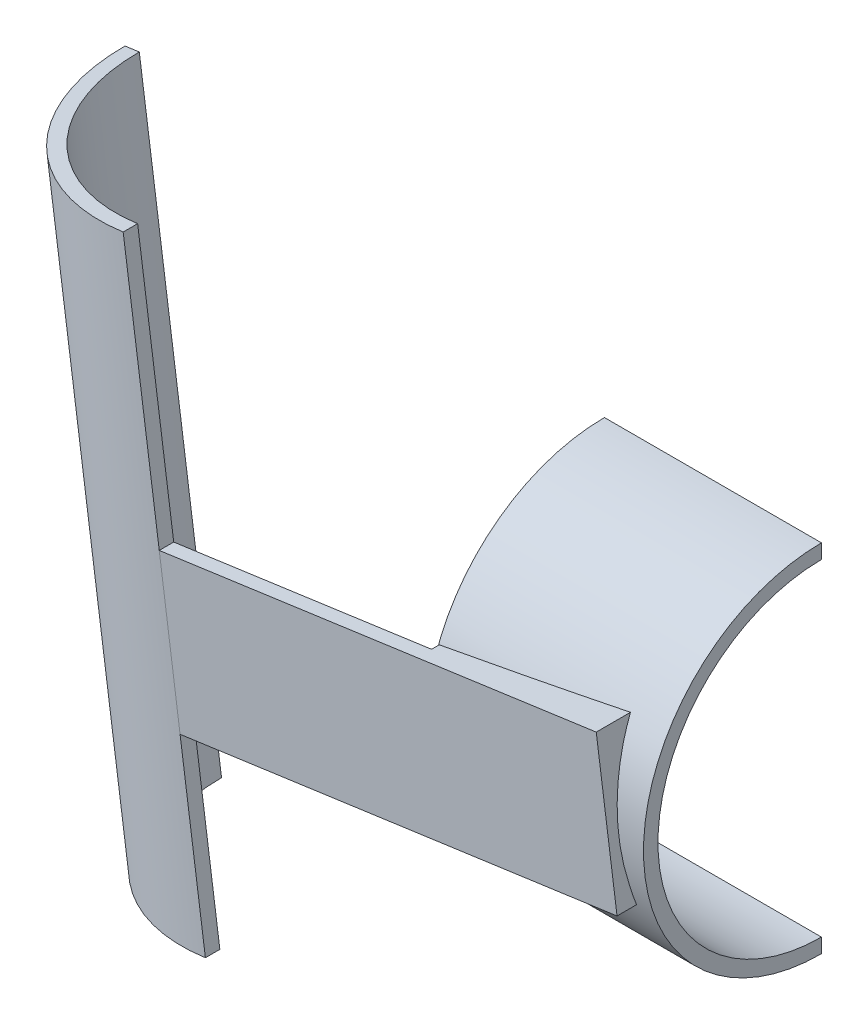
SolidWorks part; units mm, degrees
ref_plane "Front Plane" through (0, 0, 0) normal (0, 0, 1) x (1, 0, 0)
ref_plane "Top Plane" through (0, 0, 0) normal (0, 1, 0) x (1, 0, 0)
ref_plane "Right Plane" through (0, 0, 0) normal (1, 0, 0) x (0, 0, -1)
sketch "Sketch1" plane through (0, 0, 0) normal (0, 0, 1) x (1, 0, 0)
  line L0 (455.4819, 880.2488) -> (455.4819, 835.5488) construction
  line L1 (391.4041, 894.3046) -> (438.4454, 900.8896) construction
  line L2 (391.4041, 894.3046) -> (402.7935, 812.9429) construction
  line L3 (438.4454, 900.8896) -> (449.8348, 819.528) construction
  line L4 (449.8348, 819.528) -> (402.7935, 812.9429) construction
  line L5 (414.9248, 897.5971) -> (426.3141, 816.2354) construction
  line L6 (455.4819, 857.8988) -> (420.4819, 857.8988) construction
  dimension "D1" = 44.7
  dimension "D2" = 47.5
  dimension "D3" = 35
ref_plane "Plane1" through (455.4819, 0, 0) normal (1, 0, 0) x (0, 0, -1)
ref_plane "Plane2" through (-103.8709, 742.0178, 0) normal (0.1386, -0.9903, 0) x (-0.9903, -0.1386, 0)
sketch "Sketch2" plane through (455.4819, 0, 0) normal (1, 0, 0) x (0, 0, -1)
  circle A0 centre (0, 857.8988) radius 22.6
  circle A1 centre (0, 857.8988) radius 24.6
  dimension "D1" = 2
  dimension "D2" = 45.2
sketch "Sketch3" plane through (-103.8709, 742.0178, 0) normal (0.1386, -0.9903, 0) x (-0.9903, -0.1386, 0)
  line L0 (-559.1045, 0) -> (-511.6045, 0) construction
  circle A0 centre (-535.3545, 0) radius 24
  circle A1 centre (-535.3545, 0) radius 26
  dimension "D1" = 2
  dimension "D2" = 48
extrude "Boss-Extrude1" add sketch "Sketch3" against normal blind 82
extrude "Boss-Extrude2" add sketch "Sketch2" along normal blind 30 separate body
sketch "Sketch4" plane through (0, 0, 0) normal (0, 0, 1) x (1, 0, 0)
  line L0 (414.9248, 897.5971) -> (426.3141, 816.2354)
  line L1 (426.3141, 816.2354) -> (452.0631, 819.8399)
  line L2 (-129.7436, 738.396) -> (-77.9982, 745.6396) construction
  line L3 (452.0631, 819.8399) -> (440.6737, 901.2016)
  line L4 (414.9248, 897.5971) -> (440.6737, 901.2016)
  line L5 (452.0631, 819.8399) -> (440.6952, 901.0481) construction
extrude "Cut-Extrude1" cut sketch "Sketch4" against normal blind 30 and the other way blind 30
sketch "Sketch5" plane through (0, 0, 0) normal (0, 0, 1) x (1, 0, 0)
  line L1 (488.3236, 809.3216) -> (386.5072, 809.3216)
  line L2 (488.3236, 809.3216) -> (488.3236, 900.138)
  line L3 (488.3236, 900.138) -> (386.5072, 900.138)
  line L4 (386.5072, 809.3216) -> (386.5072, 900.138)
extrude "Cut-Extrude2" cut sketch "Sketch5" against normal blind 30
sketch "Sketch6" plane through (530.185, 74.2176, 0) normal (0.9903, 0.1386, 0) x (0, 0, -1)
  line L0 (-24, 749.2527) -> (-24, 831.2527) construction
  line L1 (-24, 795.2774) -> (-26, 795.2774)
  line L2 (-24, 795.2774) -> (-24, 774.5022)
  line L3 (-24, 774.5022) -> (-26, 774.5022)
  line L4 (-26, 795.2774) -> (-26, 774.5022)
  line L5 (-26, 749.2527) -> (-26, 831.2527) construction
extrude "Boss-Extrude3" add sketch "Sketch6" along normal blind 61
sketch "Sketch7" plane through (590.596, 82.6742, 0) normal (0.9903, 0.1386, 0) x (0, 0, -1)
  line L2 (-26, 774.5022) -> (-26, 795.2774)
  line L3 (-26, 795.2774) -> (-20.1913, 795.2774)
  line L4 (-26, 774.5022) -> (-23.3021, 774.5022)
  arc A1 (-23.3021, 774.5022) -> (-20.1913, 795.2774) centre (-0.2364, 781.669) cw
  ellipse E0 centre (0, 782.3111) end of major axis (-24.6, 782.3111) minor radius 24.3625 (0, 806.6736) -> (0, 757.9487) ccw construction
extrude "Boss-Extrude5" add sketch "Sketch7" against normal blind 25
sketch "Sketch8" plane through (485.4819, 0, 0) normal (1, 0, 0) x (0, 0, -1)
  circle A0 centre (0, 857.8988) radius 22.6
extrude "Cut-Extrude3" cut sketch "Sketch8" against normal blind 32
